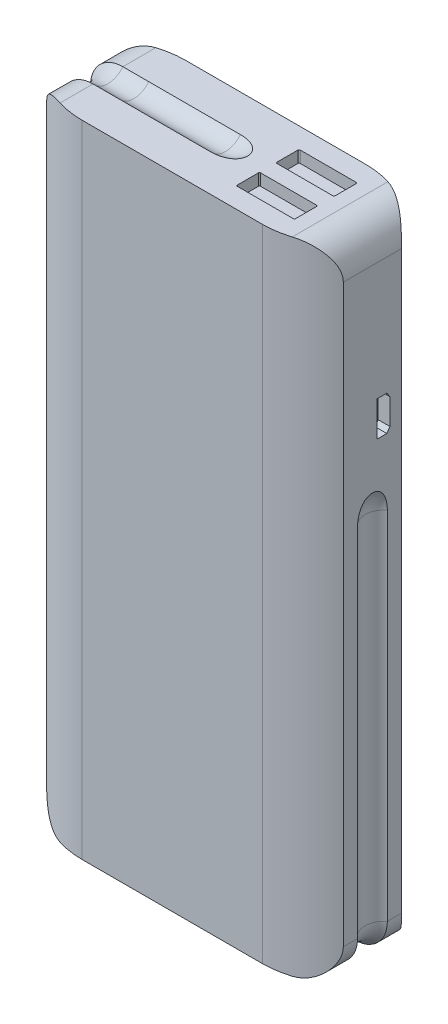
SolidWorks part; units mm, degrees
ref_plane "Front Plane" through (0, 0, 0) normal (0, 0, 1) x (1, 0, 0)
ref_plane "Top Plane" through (0, 0, 0) normal (0, 1, 0) x (1, 0, 0)
ref_plane "Right Plane" through (0, 0, 0) normal (1, 0, 0) x (0, 0, -1)
sketch "Sketch1" plane through (0, 0, 0) normal (0, 1, 0) x (1, 0, 0)
  line L0 (-32.385, 0) -> (32.385, 0) construction
  line L1 (-32.385, -11.303) -> (32.385, -11.303)
  line L2 (-32.385, -11.303) -> (-32.385, 11.303)
  line L3 (-32.385, 11.303) -> (32.385, 11.303)
  line L4 (32.385, -11.303) -> (32.385, 11.303)
  line L5 (-32.385, -11.303) -> (32.385, 11.303) construction
  line L6 (-32.385, 11.303) -> (32.385, -11.303) construction
  line L7 (0, 11.303) -> (0, -11.303) construction
  arc A1 (-19.685, -11.303) -> (-32.385, -6.35) centre (-19.685, 7.4556) cw
  arc A2 (-19.685, 11.303) -> (-32.385, 6.35) centre (-19.685, -7.4556) ccw
  arc A3 (19.685, 11.303) -> (32.385, 6.35) centre (19.685, -7.4556) cw
  arc A4 (19.685, -11.303) -> (32.385, -6.35) centre (19.685, 7.4556) ccw
  point P0 (0, 0)
  dimension "D3" = 4.953
  dimension "D1" = 64.77
  dimension "D2" = 22.606
  dimension "D4" = 12.7
extrude "Boss-Extrude1" add sketch "Sketch1" along normal blind 139.7 contours L1 A4 L4 A3 L3 A2 L2 A1 region at (0, 0, 0)
sketch "Sketch2" plane through (0, 0, 11.303) normal (0, 0, 1) x (1, 0, 0)
  line L0 (-32.385, 139.7) -> (-32.385, 0) construction
  line L1 (32.385, 139.7) -> (32.385, 0) construction
  line L2 (-32.385, 132.6388) -> (-32.385, 7.0612)
  line L3 (32.385, 132.6388) -> (32.385, 7.0612)
  line L5 (32.385, 0) -> (-32.385, 0)
  line L6 (32.385, 0) -> (32.385, 139.7)
  line L7 (32.385, 139.7) -> (-32.385, 139.7)
  line L12 (25.3238, 0) -> (-25.3238, 0)
  line L13 (25.3238, 139.7) -> (-25.3238, 139.7)
  line L14 (-32.385, 0) -> (-32.385, 139.7)
  arc A0 (-32.385, 132.6388) -> (-25.3238, 139.7) centre (-25.3238, 132.6388) cw
  arc A1 (-32.385, 7.0612) -> (-25.3238, 0) centre (-25.3238, 7.0612) ccw
  arc A2 (32.385, 7.0612) -> (25.3238, 0) centre (25.3238, 7.0612) cw
  arc A3 (32.385, 132.6388) -> (25.3238, 139.7) centre (25.3238, 132.6388) ccw
  point P2 (-32.385, 139.7)
  point P18 (32.385, 0)
  dimension "D1" = 7.0612
extrude "Cut-Extrude1" cut sketch "Sketch2" against normal through all contours L14 A0 L7 | A3 L6 L7 | L6 A2 L5 | A1 L14 L5 region at (-30.8078, 138.1228, 11.303) region at (-30.8078, 1.5772, 11.303) region at (30.8078, 138.1228, 11.303) region at (30.8078, 1.5772, 11.303)
sketch "Sketch4" plane through (0, 139.7, 0) normal (0, 1, 0) x (1, 0, 0)
  line L0 (0, 0) -> (26.2714, 0) construction
  line L1 (21.971, -6.858) -> (9.779, -6.858)
  line L2 (22.225, -6.604) -> (22.225, -2.032)
  line L3 (21.971, -1.778) -> (9.779, -1.778)
  line L4 (9.525, -6.604) -> (9.525, -2.032)
  line L5 (32.385, 6.35) -> (32.385, -6.35) construction
  line L6 (9.525, 6.604) -> (9.525, 2.032)
  line L7 (21.971, 1.778) -> (9.779, 1.778)
  line L8 (22.225, 6.604) -> (22.225, 2.032)
  line L9 (21.971, 6.858) -> (9.779, 6.858)
  arc A0 (22.225, -2.032) -> (21.971, -1.778) centre (21.971, -2.032) ccw
  arc A1 (9.779, -1.778) -> (9.525, -2.032) centre (9.779, -2.032) ccw
  arc A2 (9.779, -6.858) -> (9.525, -6.604) centre (9.779, -6.604) cw
  arc A3 (21.971, -6.858) -> (22.225, -6.604) centre (21.971, -6.604) ccw
  arc A4 (21.971, 6.858) -> (22.225, 6.604) centre (21.971, 6.604) cw
  arc A5 (9.779, 6.858) -> (9.525, 6.604) centre (9.779, 6.604) ccw
  arc A6 (9.779, 1.778) -> (9.525, 2.032) centre (9.779, 2.032) cw
  arc A7 (22.225, 2.032) -> (21.971, 1.778) centre (21.971, 2.032) cw
  point P11 (22.225, -1.778)
  point P16 (9.525, -6.858)
  point P19 (22.225, -6.858)
  point P32 (22.225, 6.858)
  point P33 (9.525, 6.858)
  point P34 (22.225, 1.778)
  dimension "D5" = 0.254
  dimension "D1" = 12.7
  dimension "D2" = 5.08
  dimension "D3" = 1.778
  dimension "D4" = 10.16
extrude "Cut-Extrude2" cut sketch "Sketch4" against normal blind 2.54
sketch "Sketch3" plane through (0, 0, 0) normal (0, 0, 1) x (1, 0, 0)
  line L8 (-19.685, 142.24) -> (0.3175, 142.24)
  line L10 (34.925, 84.7725) -> (34.925, 7.0612)
  line L11 (39.0525, 88.9) -> (43.1995, 88.9)
  line L12 (4.445, 146.3675) -> (4.445, 151.2241)
  line L16 (25.3238, 142.24) -> (19.685, 142.24)
  line L17 (19.685, 142.24) -> (-19.685, 142.24)
  line L18 (-19.685, 142.24) -> (-25.3238, 142.24)
  line L19 (-34.925, 132.6388) -> (-34.925, 7.0612)
  line L20 (-25.3238, -2.54) -> (-19.685, -2.54)
  line L21 (-19.685, -2.54) -> (19.685, -2.54)
  line L22 (19.685, -2.54) -> (25.3238, -2.54)
  line L23 (34.925, 7.0612) -> (34.925, 132.6388)
  line L26 (-19.685, 142.24) -> (-25.3238, 142.24)
  line L27 (-34.925, 132.6388) -> (-34.925, 7.0612)
  line L28 (-25.3238, -2.54) -> (-19.685, -2.54)
  line L29 (-19.685, -2.54) -> (19.685, -2.54)
  line L30 (19.685, -2.54) -> (25.3238, -2.54)
  arc A4 (0.3175, 142.24) -> (4.445, 146.3675) centre (0.3175, 146.3675) ccw
  arc A5 (39.0525, 88.9) -> (34.925, 84.7725) centre (39.0525, 84.7725) ccw
  arc A8 (34.925, 132.6388) -> (25.3238, 142.24) centre (25.3238, 132.6388) ccw
  arc A9 (-25.3238, 142.24) -> (-34.925, 132.6388) centre (-25.3238, 132.6388) ccw
  arc A10 (-34.925, 7.0612) -> (-25.3238, -2.54) centre (-25.3238, 7.0612) ccw
  arc A11 (25.3238, -2.54) -> (34.925, 7.0612) centre (25.3238, 7.0612) ccw
  arc A13 (-25.3238, 142.24) -> (-34.925, 132.6388) centre (-25.3238, 132.6388) ccw
  arc A14 (-34.925, 7.0612) -> (-25.3238, -2.54) centre (-25.3238, 7.0612) ccw
  arc A15 (25.3238, -2.54) -> (34.925, 7.0612) centre (25.3238, 7.0612) ccw
  point P0 (4.445, 142.24)
  point P1 (34.925, 88.9)
  point P8 (4.445, 142.24)
  point P11 (34.925, 88.9)
  dimension "D4" = 4.1275
  dimension "D2" = 5.08
  dimension "D3" = 81.8388
  dimension "D1" = 2.54
ref_plane "Plane1" through (43.1995, 0, 0) normal (1, 0, 0) x (0, 0, -1)
sketch "Sketch5" plane through (43.1995, 0, 0) normal (1, 0, 0) x (0, 0, -1)
  circle A0 centre (0, 88.9) radius 4.1275
  dimension "D1" = 8.255
sweep "Cut-Sweep1" cut profiles "Sketch5" path "Sketch3"
sketch "Sketch6" plane through (32.385, 0, 0) normal (1, 0, 0) x (0, 0, -1)
  line L0 (1.016, 99.3054) -> (1.016, 106.9254)
  line L1 (1.016, 106.9254) -> (3.1369, 106.9254)
  line L2 (3.1369, 106.9254) -> (3.81, 105.9348)
  line L3 (3.81, 105.9348) -> (3.81, 100.296)
  line L4 (3.81, 100.296) -> (3.1369, 99.3054)
  line L5 (3.1369, 99.3054) -> (1.016, 99.3054)
  line L6 (6.35, 132.6388) -> (6.35, 7.0612) construction
  point P6 (3.81, 103.1154)
  point P7 (1.016, 103.1154)
  dimension "D1" = 7.62
  dimension "D2" = 2.1209
  dimension "D3" = 2.1209
  dimension "D4" = 2.794
  dimension "D5" = 5.6388
  dimension "D6" = 3.81
  dimension "D7" = 2.54
extrude "Cut-Extrude3" cut sketch "Sketch6" against normal blind 2.54
ref_point "Point1"
ref_point "Point2"
ref_axis "Axis1" through (0, 69.85, -11.303) along (0, 0, 1)
